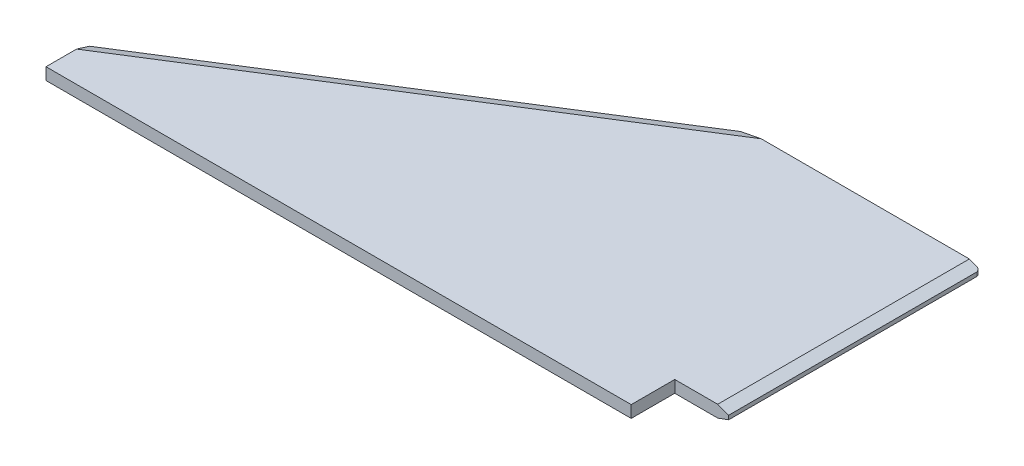
SolidWorks part; units mm, degrees
material "A-Glass Fiber"
ref_plane "Front Plane" through (0, 0, 0) normal (0, 0, 1) x (1, 0, 0)
ref_plane "Top Plane" through (0, 0, 0) normal (0, 1, 0) x (1, 0, 0)
ref_plane "Right Plane" through (0, 0, 0) normal (1, 0, 0) x (0, 0, -1)
sketch "Sketch1" plane through (0, 0, 0) normal (0, 1, 0) x (1, 0, 0)
  line L0 (0, 0) -> (0, 10.9)
  line L1 (0, 10.9) -> (100, 73.9)
  line L2 (100, 73.9) -> (160, 73.9)
  line L3 (160, 73.9) -> (160, 10.9)
  line L7 (160, 10.9) -> (146.5, 10.9)
  line L9 (146.5, 0) -> (0, 0)
  line L10 (-989.0676, -29) -> (49010.9324, -29) construction
  line L11 (-1000, 0) -> (49000, 0) construction
  line L12 (-999.3384, -58) -> (49000.6616, -58) construction
  line L13 (0, 0) -> (0, -58) construction
  line L15 (146.5, 0) -> (146.5, 10.9)
  point P6 (160.3109, 10.9)
  point P11 (160, 0)
  point P15 (0, -29)
  dimension "D1" = 60
  dimension "D2" = 160
  dimension "D3" = 13.5
  dimension "D4" = 100
  dimension "D5" = 63
  dimension "D6" = 79.8
  dimension "D7" = 58
extrude "Boss-Extrude1" add sketch "Sketch1" along normal blind 3
chamfer "Chamfer1" distance 1 angle 70 2 edges at (160, 3, -42.4) (50, 3, -42.4) first distance on face at (160, 1.5, -42.4) first distance on face at (50, 1.5, -42.4)
chamfer "Chamfer2" distance 1 angle 70 2 edges at (50, 0, -42.4) (160, 0, -42.4) first distance on face at (50, 1, -42.4) first distance on face at (160, 1, -42.4)
fillet "Fillet1" radius 1 1 edges at (160, 1.5, -73.9)
